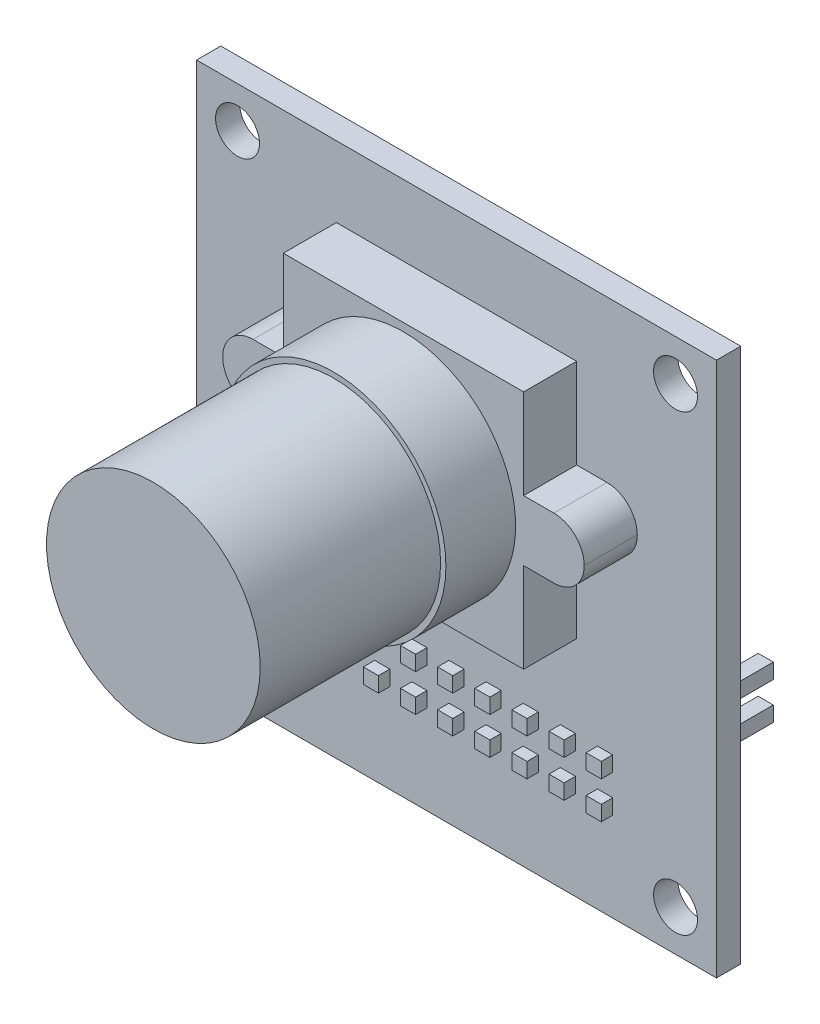
SolidWorks part; units mm, degrees
ref_plane "Front Plane" through (0, 0, 0) normal (0, 0, 1) x (1, 0, 0)
ref_plane "Top Plane" through (0, 0, 0) normal (0, 1, 0) x (1, 0, 0)
ref_plane "Right Plane" through (0, 0, 0) normal (1, 0, 0) x (0, 0, -1)
sketch "Sketch1" plane through (0, 0, 0) normal (0, 0, 1) x (1, 0, 0)
  line L1 (-17.15, -22.7) -> (17.15, -22.7)
  line L2 (-17.15, -22.7) -> (-17.15, 12.6)
  line L3 (-17.15, 12.6) -> (17.15, 12.6)
  line L4 (17.15, -22.7) -> (17.15, 12.6)
  line L5 (-17.15, -22.7) -> (17.15, 12.6) construction
  line L6 (-17.15, 12.6) -> (17.15, -22.7) construction
  point P0 (0, -5.05)
  dimension "D1" = 35.3
  dimension "D2" = 34.3
  dimension "D3" = 12.6
extrude "Boss-Extrude1" add sketch "Sketch1" along normal blind 1.6
sketch "Sketch2" plane through (0, 0, 0) normal (0, 0, -1) x (-1, 0, 0)
  line L0 (17.15, -22.7) -> (-17.15, -22.7) construction
  line L1 (-11.3, -12.6) -> (11.3, -12.6)
  line L2 (-11.3, -12.6) -> (-11.3, -17.6)
  line L3 (-11.3, -17.6) -> (11.3, -17.6)
  line L4 (11.3, -12.6) -> (11.3, -17.6)
  line L5 (-11.3, -12.6) -> (11.3, -17.6) construction
  line L6 (-11.3, -17.6) -> (11.3, -12.6) construction
  point P0 (0, -15.1)
  dimension "D1" = 5
  dimension "D2" = 22.6
  dimension "D3" = 5.1
extrude "Boss-Extrude2" add sketch "Sketch2" along normal blind 3
sketch "Sketch3" plane through (0, 0, -3) normal (0, 0, -1) x (-1, 0, 0)
  line L0 (-7.85, -16.825) -> (-7.85, -15.825)
  line L1 (-10.3, -16.825) -> (-9.3, -16.825)
  line L3 (-10.3, -16.825) -> (-10.3, -15.825)
  line L4 (-10.3, -15.825) -> (-9.3, -15.825)
  line L5 (-9.3, -16.825) -> (-9.3, -15.825)
  line L6 (-10.3, -16.825) -> (-9.3, -15.825) construction
  line L7 (-10.3, -15.825) -> (-9.3, -16.825) construction
  line L8 (-7.85, -16.825) -> (-6.85, -16.825)
  line L9 (-6.85, -16.825) -> (-6.85, -15.825)
  line L10 (-7.85, -15.825) -> (-6.85, -15.825)
  line L11 (-5.4, -16.825) -> (-5.4, -15.825)
  line L12 (-5.4, -16.825) -> (-4.4, -16.825)
  line L13 (-4.4, -16.825) -> (-4.4, -15.825)
  line L14 (-5.4, -15.825) -> (-4.4, -15.825)
  line L15 (-2.95, -16.825) -> (-2.95, -15.825)
  line L16 (-2.95, -16.825) -> (-1.95, -16.825)
  line L17 (-1.95, -16.825) -> (-1.95, -15.825)
  line L18 (-2.95, -15.825) -> (-1.95, -15.825)
  line L19 (-0.5, -16.825) -> (-0.5, -15.825)
  line L20 (-0.5, -16.825) -> (0.5, -16.825)
  line L21 (0.5, -16.825) -> (0.5, -15.825)
  line L22 (-0.5, -15.825) -> (0.5, -15.825)
  line L23 (1.95, -16.825) -> (1.95, -15.825)
  line L24 (1.95, -16.825) -> (2.95, -16.825)
  line L25 (2.95, -16.825) -> (2.95, -15.825)
  line L26 (1.95, -15.825) -> (2.95, -15.825)
  line L27 (4.4, -16.825) -> (4.4, -15.825)
  line L28 (4.4, -16.825) -> (5.4, -16.825)
  line L29 (5.4, -16.825) -> (5.4, -15.825)
  line L30 (4.4, -15.825) -> (5.4, -15.825)
  line L31 (6.85, -16.825) -> (6.85, -15.825)
  line L32 (6.85, -16.825) -> (7.85, -16.825)
  line L33 (7.85, -16.825) -> (7.85, -15.825)
  line L34 (6.85, -15.825) -> (7.85, -15.825)
  line L35 (9.3, -16.825) -> (9.3, -15.825)
  line L36 (9.3, -16.825) -> (10.3, -16.825)
  line L37 (10.3, -16.825) -> (10.3, -15.825)
  line L38 (9.3, -15.825) -> (10.3, -15.825)
  line L39 (-7.85, -14.375) -> (-7.85, -13.375)
  line L40 (-7.85, -14.375) -> (-6.85, -14.375)
  line L41 (-6.85, -14.375) -> (-6.85, -13.375)
  line L42 (-7.85, -13.375) -> (-6.85, -13.375)
  line L43 (-5.4, -14.375) -> (-5.4, -13.375)
  line L44 (-5.4, -14.375) -> (-4.4, -14.375)
  line L45 (-4.4, -14.375) -> (-4.4, -13.375)
  line L46 (-5.4, -13.375) -> (-4.4, -13.375)
  line L47 (-2.95, -14.375) -> (-2.95, -13.375)
  line L48 (-2.95, -14.375) -> (-1.95, -14.375)
  line L49 (-1.95, -14.375) -> (-1.95, -13.375)
  line L50 (-2.95, -13.375) -> (-1.95, -13.375)
  line L51 (-0.5, -14.375) -> (-0.5, -13.375)
  line L52 (-0.5, -14.375) -> (0.5, -14.375)
  line L53 (0.5, -14.375) -> (0.5, -13.375)
  line L54 (-0.5, -13.375) -> (0.5, -13.375)
  line L55 (1.95, -14.375) -> (1.95, -13.375)
  line L56 (1.95, -14.375) -> (2.95, -14.375)
  line L57 (2.95, -14.375) -> (2.95, -13.375)
  line L58 (1.95, -13.375) -> (2.95, -13.375)
  line L59 (4.4, -14.375) -> (4.4, -13.375)
  line L60 (4.4, -14.375) -> (5.4, -14.375)
  line L61 (5.4, -14.375) -> (5.4, -13.375)
  line L62 (4.4, -13.375) -> (5.4, -13.375)
  line L63 (6.85, -14.375) -> (6.85, -13.375)
  line L64 (6.85, -14.375) -> (7.85, -14.375)
  line L65 (7.85, -14.375) -> (7.85, -13.375)
  line L66 (6.85, -13.375) -> (7.85, -13.375)
  line L67 (9.3, -14.375) -> (9.3, -13.375)
  line L68 (9.3, -14.375) -> (10.3, -14.375)
  line L69 (10.3, -14.375) -> (10.3, -13.375)
  line L70 (9.3, -13.375) -> (10.3, -13.375)
  line L71 (-10.3, -14.375) -> (-10.3, -13.375)
  line L72 (-10.3, -14.375) -> (-9.3, -14.375)
  line L73 (-9.3, -14.375) -> (-9.3, -13.375)
  line L74 (-10.3, -13.375) -> (-9.3, -13.375)
  line L75 (0, -16.825) -> (0, -13.375) construction
  line L76 (0, -15.1) -> (11.3, -15.1) construction
  line L77 (11.3, -17.6) -> (11.3, -12.6) construction
  point P0 (-9.8, -16.325)
  dimension "D1" = 1
  dimension "D5" = 2.45
  dimension "D4" = 2.45
  dimension "D2" = 9
  dimension "D3" = 2
extrude "Boss-Extrude3" add sketch "Sketch3" along normal blind 6
sketch "Sketch4" plane through (0, 0, 1.6) normal (0, 0, 1) x (1, 0, 0)
  circle A0 centre (0, 0) radius 7.05
  dimension "D1" = 14.1
extrude "Boss-Extrude4" add sketch "Sketch4" along normal blind 20
sketch "Sketch5" plane through (0, 0, 1.6) normal (0, 0, 1) x (1, 0, 0)
  circle A0 centre (0, 0) radius 7.4
  dimension "D1" = 14.8
extrude "Boss-Extrude5" add sketch "Sketch5" along normal blind 8.1
sketch "Sketch6" plane through (0, 0, 1.6) normal (0, 0, 1) x (1, 0, 0)
  line L0 (0, 0) -> (0, 7.925) construction
  line L1 (7.925, 7.925) -> (-7.925, 7.925)
  line L2 (7.925, 7.925) -> (7.925, 2)
  line L3 (7.925, -7.925) -> (-7.925, -7.925)
  line L4 (-7.925, 7.925) -> (-7.925, 2)
  line L5 (7.925, 7.925) -> (-7.925, -7.925) construction
  line L6 (7.925, -7.925) -> (-7.925, 7.925) construction
  line L7 (11.925, 2) -> (7.925, 2)
  line L8 (11.925, 2) -> (11.925, -2)
  line L9 (11.925, -2) -> (7.925, -2)
  line L11 (11.925, 2) -> (7.925, -2) construction
  line L12 (11.925, -2) -> (7.925, 2) construction
  line L13 (-11.925, -2) -> (-7.925, -2)
  line L15 (-11.925, 2) -> (-7.925, 2)
  line L16 (-11.925, 2) -> (-11.925, -2)
  line L17 (7.925, -2) -> (7.925, -7.925)
  line L18 (-7.925, -2) -> (-7.925, -7.925)
  point P0 (0, 0)
  point P6 (9.925, 0)
  dimension "D1" = 15.85
  dimension "D2" = 4
  dimension "D3" = 15.85
extrude "Boss-Extrude6" add sketch "Sketch6" along normal blind 3.5
fillet "Fillet1" radius 2 4 edges at (11.925, 2, 3.35) (11.925, -2, 3.35) (-11.925, 2, 3.35) (-11.925, -2, 3.35)
sketch "Sketch7" plane through (0, 0, 1.6) normal (0, 0, 1) x (1, 0, 0)
  line L4 (5.4, -16.825) -> (5.4, -15.825)
  line L5 (5.4, -15.825) -> (4.4, -15.825)
  line L6 (4.4, -15.825) -> (4.4, -16.825)
  line L7 (4.4, -16.825) -> (5.4, -16.825)
  line L8 (5.4, -16.825) -> (5.4, -15.825)
  line L9 (5.4, -15.825) -> (4.4, -15.825)
  line L10 (4.4, -15.825) -> (4.4, -16.825)
  line L11 (4.4, -16.825) -> (5.4, -16.825)
  line L12 (9.3, -16.825) -> (10.3, -16.825)
  line L13 (9.3, -15.825) -> (9.3, -16.825)
  line L14 (10.3, -15.825) -> (9.3, -15.825)
  line L15 (10.3, -16.825) -> (10.3, -15.825)
  line L16 (9.3, -16.825) -> (10.3, -16.825)
  line L17 (9.3, -15.825) -> (9.3, -16.825)
  line L18 (10.3, -15.825) -> (9.3, -15.825)
  line L19 (10.3, -16.825) -> (10.3, -15.825)
  line L20 (7.85, -16.825) -> (7.85, -15.825)
  line L21 (7.85, -15.825) -> (6.85, -15.825)
  line L22 (6.85, -15.825) -> (6.85, -16.825)
  line L23 (6.85, -16.825) -> (7.85, -16.825)
  line L24 (7.85, -16.825) -> (7.85, -15.825)
  line L25 (7.85, -15.825) -> (6.85, -15.825)
  line L26 (6.85, -15.825) -> (6.85, -16.825)
  line L27 (6.85, -16.825) -> (7.85, -16.825)
  line L28 (-4.4, -16.825) -> (-4.4, -15.825)
  line L29 (-4.4, -15.825) -> (-5.4, -15.825)
  line L30 (-5.4, -15.825) -> (-5.4, -16.825)
  line L31 (-5.4, -16.825) -> (-4.4, -16.825)
  line L32 (-4.4, -16.825) -> (-4.4, -15.825)
  line L33 (-4.4, -15.825) -> (-5.4, -15.825)
  line L34 (-5.4, -15.825) -> (-5.4, -16.825)
  line L35 (-5.4, -16.825) -> (-4.4, -16.825)
  line L36 (-1.95, -16.825) -> (-1.95, -15.825)
  line L37 (-1.95, -15.825) -> (-2.95, -15.825)
  line L38 (-2.95, -15.825) -> (-2.95, -16.825)
  line L39 (-2.95, -16.825) -> (-1.95, -16.825)
  line L40 (-1.95, -16.825) -> (-1.95, -15.825)
  line L41 (-1.95, -15.825) -> (-2.95, -15.825)
  line L42 (-2.95, -15.825) -> (-2.95, -16.825)
  line L43 (-2.95, -16.825) -> (-1.95, -16.825)
  line L44 (0.5, -16.825) -> (0.5, -15.825)
  line L45 (0.5, -15.825) -> (-0.5, -15.825)
  line L46 (-0.5, -15.825) -> (-0.5, -16.825)
  line L47 (-0.5, -16.825) -> (0.5, -16.825)
  line L48 (0.5, -16.825) -> (0.5, -15.825)
  line L49 (0.5, -15.825) -> (-0.5, -15.825)
  line L50 (-0.5, -15.825) -> (-0.5, -16.825)
  line L51 (-0.5, -16.825) -> (0.5, -16.825)
  line L52 (2.95, -16.825) -> (2.95, -15.825)
  line L53 (2.95, -15.825) -> (1.95, -15.825)
  line L54 (1.95, -15.825) -> (1.95, -16.825)
  line L55 (1.95, -16.825) -> (2.95, -16.825)
  line L56 (2.95, -16.825) -> (2.95, -15.825)
  line L57 (2.95, -15.825) -> (1.95, -15.825)
  line L58 (1.95, -15.825) -> (1.95, -16.825)
  line L59 (1.95, -16.825) -> (2.95, -16.825)
  line L60 (-9.3, -16.825) -> (-9.3, -15.825)
  line L61 (-9.3, -15.825) -> (-10.3, -15.825)
  line L62 (-10.3, -15.825) -> (-10.3, -16.825)
  line L63 (-10.3, -16.825) -> (-9.3, -16.825)
  line L64 (-9.3, -16.825) -> (-9.3, -15.825)
  line L65 (-9.3, -15.825) -> (-10.3, -15.825)
  line L66 (-10.3, -15.825) -> (-10.3, -16.825)
  line L67 (-10.3, -16.825) -> (-9.3, -16.825)
  line L68 (-6.85, -16.825) -> (-6.85, -15.825)
  line L69 (-6.85, -15.825) -> (-7.85, -15.825)
  line L70 (-7.85, -15.825) -> (-7.85, -16.825)
  line L71 (-7.85, -16.825) -> (-6.85, -16.825)
  line L72 (-6.85, -16.825) -> (-6.85, -15.825)
  line L73 (-6.85, -15.825) -> (-7.85, -15.825)
  line L74 (-7.85, -15.825) -> (-7.85, -16.825)
  line L75 (-7.85, -16.825) -> (-6.85, -16.825)
  line L76 (5.4, -14.375) -> (5.4, -13.375)
  line L77 (5.4, -13.375) -> (4.4, -13.375)
  line L78 (4.4, -13.375) -> (4.4, -14.375)
  line L79 (4.4, -14.375) -> (5.4, -14.375)
  line L80 (5.4, -14.375) -> (5.4, -13.375)
  line L81 (5.4, -13.375) -> (4.4, -13.375)
  line L82 (4.4, -13.375) -> (4.4, -14.375)
  line L83 (4.4, -14.375) -> (5.4, -14.375)
  line L84 (7.85, -14.375) -> (7.85, -13.375)
  line L85 (6.85, -14.375) -> (7.85, -14.375)
  line L86 (6.85, -13.375) -> (6.85, -14.375)
  line L87 (7.85, -13.375) -> (6.85, -13.375)
  line L88 (7.85, -14.375) -> (7.85, -13.375)
  line L89 (6.85, -14.375) -> (7.85, -14.375)
  line L90 (6.85, -13.375) -> (6.85, -14.375)
  line L91 (7.85, -13.375) -> (6.85, -13.375)
  line L92 (-4.4, -14.375) -> (-4.4, -13.375)
  line L93 (-4.4, -13.375) -> (-5.4, -13.375)
  line L94 (-5.4, -13.375) -> (-5.4, -14.375)
  line L95 (-5.4, -14.375) -> (-4.4, -14.375)
  line L96 (-4.4, -14.375) -> (-4.4, -13.375)
  line L97 (-4.4, -13.375) -> (-5.4, -13.375)
  line L98 (-5.4, -13.375) -> (-5.4, -14.375)
  line L99 (-5.4, -14.375) -> (-4.4, -14.375)
  line L100 (-1.95, -14.375) -> (-1.95, -13.375)
  line L101 (-1.95, -13.375) -> (-2.95, -13.375)
  line L102 (-2.95, -13.375) -> (-2.95, -14.375)
  line L103 (-2.95, -14.375) -> (-1.95, -14.375)
  line L104 (-1.95, -14.375) -> (-1.95, -13.375)
  line L105 (-1.95, -13.375) -> (-2.95, -13.375)
  line L106 (-2.95, -13.375) -> (-2.95, -14.375)
  line L107 (-2.95, -14.375) -> (-1.95, -14.375)
  line L108 (0.5, -14.375) -> (0.5, -13.375)
  line L109 (0.5, -13.375) -> (-0.5, -13.375)
  line L110 (-0.5, -13.375) -> (-0.5, -14.375)
  line L111 (-0.5, -14.375) -> (0.5, -14.375)
  line L112 (0.5, -14.375) -> (0.5, -13.375)
  line L113 (0.5, -13.375) -> (-0.5, -13.375)
  line L114 (-0.5, -13.375) -> (-0.5, -14.375)
  line L115 (-0.5, -14.375) -> (0.5, -14.375)
  line L116 (2.95, -14.375) -> (2.95, -13.375)
  line L117 (1.95, -14.375) -> (2.95, -14.375)
  line L118 (1.95, -13.375) -> (1.95, -14.375)
  line L119 (2.95, -13.375) -> (1.95, -13.375)
  line L120 (2.95, -14.375) -> (2.95, -13.375)
  line L121 (1.95, -14.375) -> (2.95, -14.375)
  line L122 (1.95, -13.375) -> (1.95, -14.375)
  line L123 (2.95, -13.375) -> (1.95, -13.375)
  line L124 (10.3, -14.375) -> (10.3, -13.375)
  line L125 (10.3, -13.375) -> (9.3, -13.375)
  line L126 (9.3, -13.375) -> (9.3, -14.375)
  line L127 (9.3, -14.375) -> (10.3, -14.375)
  line L128 (10.3, -14.375) -> (10.3, -13.375)
  line L129 (10.3, -13.375) -> (9.3, -13.375)
  line L130 (9.3, -13.375) -> (9.3, -14.375)
  line L131 (9.3, -14.375) -> (10.3, -14.375)
  line L132 (-9.3, -14.375) -> (-9.3, -13.375)
  line L133 (-9.3, -13.375) -> (-10.3, -13.375)
  line L134 (-10.3, -13.375) -> (-10.3, -14.375)
  line L135 (-10.3, -14.375) -> (-9.3, -14.375)
  line L136 (-9.3, -14.375) -> (-9.3, -13.375)
  line L137 (-9.3, -13.375) -> (-10.3, -13.375)
  line L138 (-10.3, -13.375) -> (-10.3, -14.375)
  line L139 (-10.3, -14.375) -> (-9.3, -14.375)
  line L140 (-6.85, -14.375) -> (-6.85, -13.375)
  line L141 (-7.85, -14.375) -> (-6.85, -14.375)
  line L142 (-7.85, -13.375) -> (-7.85, -14.375)
  line L143 (-6.85, -13.375) -> (-7.85, -13.375)
  line L144 (-6.85, -14.375) -> (-6.85, -13.375)
  line L145 (-7.85, -14.375) -> (-6.85, -14.375)
  line L146 (-7.85, -13.375) -> (-7.85, -14.375)
  line L147 (-6.85, -13.375) -> (-7.85, -13.375)
  dimension "D1" = 0
  dimension "D2" = 0
  dimension "D3" = 0
  dimension "D4" = 0
  dimension "D5" = 0
  dimension "D6" = 0
  dimension "D7" = 0
  dimension "D8" = 0
  dimension "D9" = 0
  dimension "D10" = 0
  dimension "D11" = 0
  dimension "D12" = 0
  dimension "D13" = 0
  dimension "D14" = 0
  dimension "D15" = 0
  dimension "D16" = 0
  dimension "D17" = 0
  dimension "D18" = 0
extrude "Boss-Extrude7" add sketch "Sketch7" along normal blind 0.75
sketch "Sketch8" plane through (0, 0, 1.6) normal (0, 0, 1) x (1, 0, 0)
  line L0 (-17.15, 12.6) -> (-17.15, -22.7) construction
  line L1 (17.15, 12.6) -> (-17.15, 12.6) construction
  line L2 (0, 0) -> (0, 12.6) construction
  line L3 (-17.15, -5.05) -> (17.15, -5.05) construction
  line L4 (17.15, -22.7) -> (17.15, 12.6) construction
  circle A0 centre (-14.45, 9.9) radius 1.45
  circle A2 centre (-14.45, -20) radius 1.45
  circle A3 centre (14.45, -20) radius 1.45
  circle A4 centre (14.45, 9.9) radius 1.45
  dimension "D1" = 2.9
  dimension "D2" = 2.7
  dimension "D3" = 2.7
extrude "Cut-Extrude1" cut sketch "Sketch8" against normal through all
